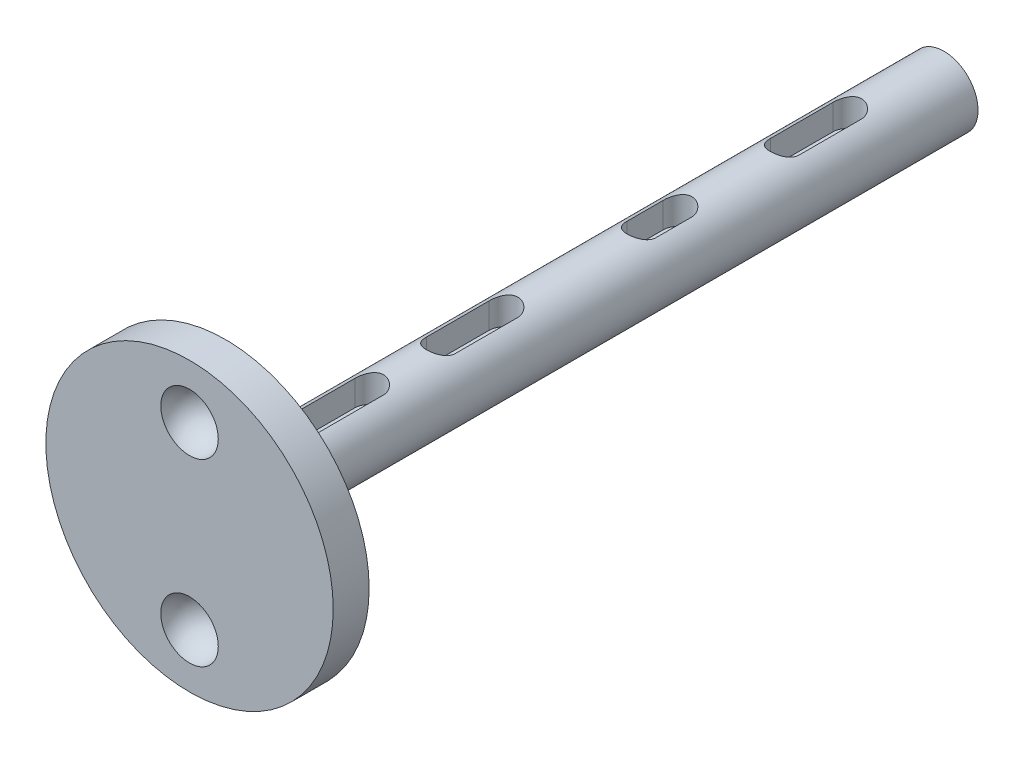
SolidWorks part; units mm, degrees
ref_plane "Front Plane" through (0, 0, 0) normal (0, 0, 1) x (1, 0, 0)
ref_plane "Top Plane" through (0, 0, 0) normal (0, 1, 0) x (1, 0, 0)
ref_plane "Right Plane" through (0, 0, 0) normal (1, 0, 0) x (0, 0, -1)
sketch "Sketch1" plane through (0, 0, 0) normal (0, 0, 1) x (1, 0, 0)
  circle A0 centre (0, 0) radius 20
  dimension "D1" = 40
extrude "Boss-Extrude1" add sketch "Sketch1" along normal blind 5
sketch "Sketch3" plane through (0, 0, 5) normal (0, 0, 1) x (1, 0, 0)
  circle A0 centre (0, 0) radius 12.5
  circle A1 centre (0, 12.5) radius 4
  circle A2 centre (0, -12.5) radius 4
  dimension "D1" = 25
  dimension "D2" = 8
  dimension "D3" = 8
extrude "Cut-Extrude2" cut sketch "Sketch3" against normal blind 4 contours A0 A1 | A0 A1 | A0 A2 | A0 A2 region at (0, 10.6924, 5) region at (0, 14.0772, 5) region at (0, -14.0772, 5) region at (0, -10.6924, 5)
fillet "Fillet2" radius 4 2 edges at (4, -12.5, 1) (4, 12.5, 1)
sketch "Sketch4" plane through (0, 0, 0) normal (0, 0, -1) x (-1, 0, 0)
  circle A0 centre (0, 0) radius 4.75
  dimension "D1" = 9.5
extrude "Boss-Extrude2" add sketch "Sketch4" along normal blind 105
ref_axis "Axis1" through (0, 0, -105) along (0, 0, 1)
ref_plane "Plane1" through (0, 4.75, 0) normal (0, 1, 0) x (1, 0, 0)
sketch "Sketch5" plane through (0, 4.75, 0) normal (0, 1, 0) x (1, 0, 0)
  line L0 (0, -4.3175) -> (0, 99.6122) construction
  line L1 (0, 10) -> (0, 20) construction
  line L2 (-2, 10) -> (-2, 20)
  line L3 (2, 10) -> (2, 20)
  line L4 (0, 30) -> (0, 38.71) construction
  line L5 (-2, 30) -> (-2, 38.71)
  line L6 (2, 30) -> (2, 38.71)
  line L7 (0, 77.83) -> (0, 86.54) construction
  line L8 (-2, 77.83) -> (-2, 86.54)
  line L9 (2, 77.83) -> (2, 86.54)
  line L10 (4.75, 0) -> (-4.75, 0) construction
  line L11 (0, 57.92) -> (0, 62.92) construction
  line L12 (-2, 57.92) -> (-2, 62.92)
  line L13 (2, 57.92) -> (2, 62.92)
  arc A0 (-2, 10) -> (2, 10) centre (0, 10) ccw
  arc A1 (2, 20) -> (-2, 20) centre (0, 20) ccw
  arc A2 (-2, 30) -> (2, 30) centre (0, 30) ccw
  arc A3 (2, 38.71) -> (-2, 38.71) centre (0, 38.71) ccw
  arc A4 (-2, 77.83) -> (2, 77.83) centre (0, 77.83) ccw
  arc A5 (2, 86.54) -> (-2, 86.54) centre (0, 86.54) ccw
  arc A6 (-2, 57.92) -> (2, 57.92) centre (0, 57.92) ccw
  arc A7 (2, 62.92) -> (-2, 62.92) centre (0, 62.92) ccw
  point P5 (0, 15)
  point P10 (0, 34.355)
  point P17 (0, 82.185)
  point P28 (0, 60.42)
  dimension "D1" = 10
  dimension "D2" = 4
  dimension "D3" = 4
  dimension "D4" = 4
  dimension "D5" = 8.71
  dimension "D6" = 8.71
  dimension "D7" = 10
  dimension "D8" = 10
  dimension "D9" = 39.12
  dimension "D10" = 21.71
  dimension "D11" = 2.5
  dimension "D12" = 4
extrude "Cut-Extrude3" cut sketch "Sketch5" against normal blind 4
sketch "Sketch6" plane through (0, 0, -105) normal (0, 0, -1) x (-1, 0, 0)
  circle A0 centre (0, 0) radius 4.75
extrude "Cut-Extrude4" cut sketch "Sketch6" against normal blind 5
